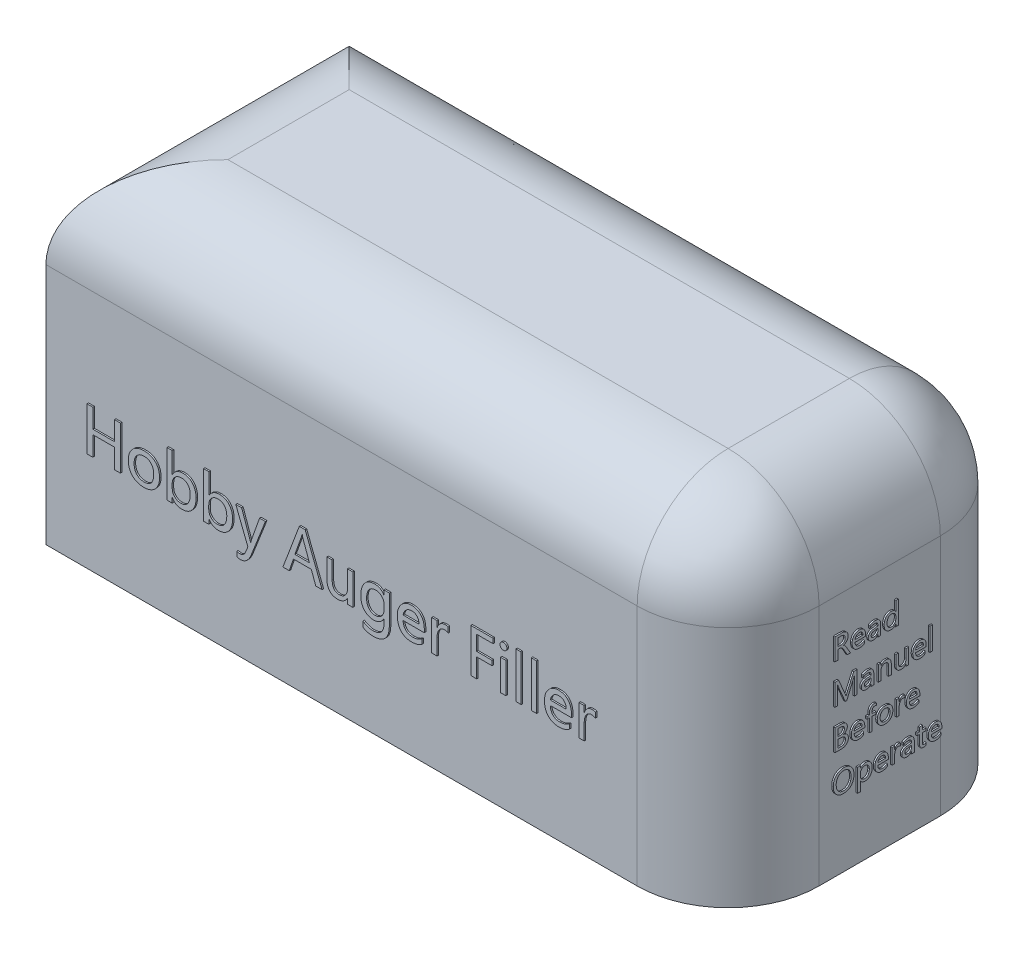
SolidWorks part; units mm, degrees
material "AISI 304"
ref_plane "前视基准面" through (0, 0, 0) normal (0, 0, 1) x (1, 0, 0)
ref_plane "上视基准面" through (0, 0, 0) normal (0, 1, 0) x (1, 0, 0)
ref_plane "右视基准面" through (0, 0, 0) normal (1, 0, 0) x (0, 0, -1)
sketch "Sketch1" plane through (0, 0, 0) normal (0, 1, 0) x (1, 0, 0)
  line L1 (-225, -100) -> (225, -100)
  line L2 (-225, -100) -> (-225, 100)
  line L3 (-225, 100) -> (225, 100)
  line L4 (225, -100) -> (225, 100)
  line L5 (-225, -100) -> (225, 100) construction
  line L6 (-225, 100) -> (225, -100) construction
  point P0 (0, 0)
  dimension "D1" = 450
  dimension "D2" = 200
extrude "Extrude1" add sketch "Sketch1" along normal blind 220
fillet "Fillet1" radius 60 2 edges at (225, 110, -100) (225, 110, 100)
fillet "Fillet2" radius 60 6 edges at (207.4264, 220, 82.4264) (-30, 220, 100) (-225, 220, 0) (-30, 220, -100) (207.4264, 220, -82.4264) (225, 220, 0)
shell "Shell1" thickness 1.2 removed face at (59.1421, 0, 0)
sketch "Sketch2" plane through (0, 0, 100) normal (0, 0, 1) x (1, 0, 0)
  text T0 "Hobby Auger Filler" font "微软雅黑" height in points 100
extrude "Extrude2" add sketch "Sketch2" along normal blind 1
sketch "Sketch3" plane through (225, 0, 0) normal (1, 0, 0) x (0, 0, -1)
  text T0 "Read \r\nManuel \r\nBefore \r\nOperate" font "微软雅黑" height in points 50
extrude "Extrude3" add sketch "Sketch3" along normal blind 1
sketch "Sketch4" plane through (0, 0, -100) normal (0, 0, -1) x (-1, 0, 0)
  text T0 "3616968" font "微软雅黑" height in points 100
extrude "Extrude4" add sketch "Sketch4" along normal blind 1
